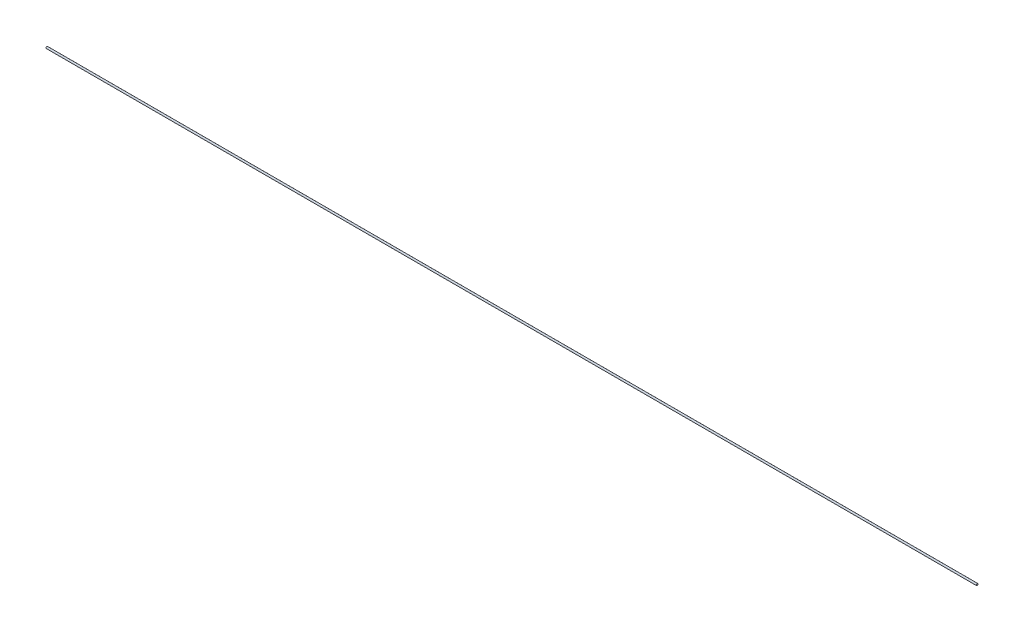
SolidWorks part; units mm, degrees
material "3.0205 (EN-AW 1200)"
ref_plane "Спереди" through (0, 0, 0) normal (0, 0, 1) x (1, 0, 0)
ref_plane "Сверху" through (0, 0, 0) normal (0, 1, 0) x (1, 0, 0)
ref_plane "Справа" through (0, 0, 0) normal (1, 0, 0) x (0, 0, -1)
sketch "Эскиз1" plane through (0, 0, 0) normal (1, 0, 0) x (0, 0, -1)
  circle A0 centre (0, 0) radius 1.5
  dimension "D1" = 3
extrude "Бобышка-Вытянуть1" add sketch "Эскиз1" along normal blind 778.215 and the other way blind 778.215
